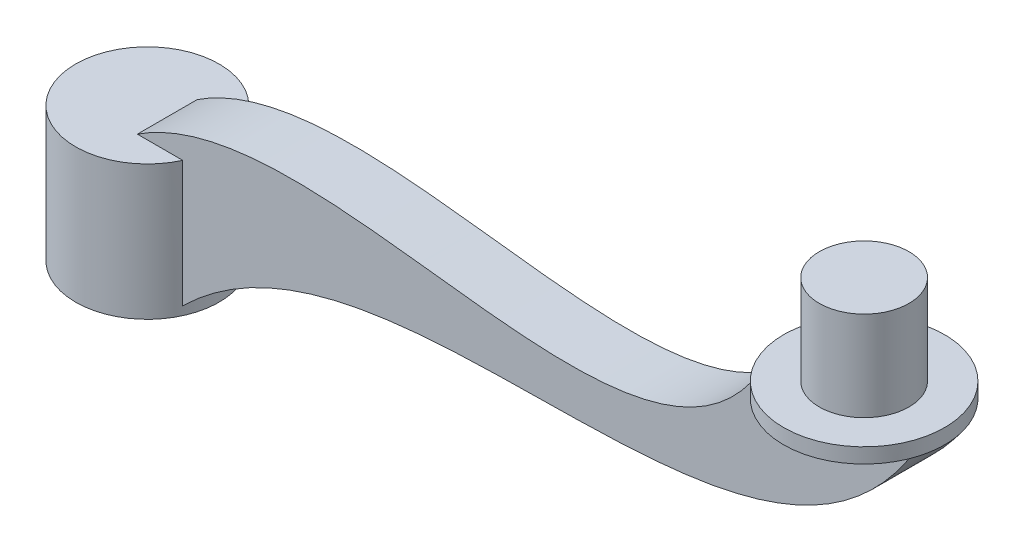
SolidWorks part; units mm, degrees
ref_plane "Front Plane" through (0, 0, 0) normal (0, 0, 1) x (1, 0, 0)
ref_plane "Top Plane" through (0, 0, 0) normal (0, 1, 0) x (1, 0, 0)
ref_plane "Right Plane" through (0, 0, 0) normal (1, 0, 0) x (0, 0, -1)
sketch "Sketch1" plane through (0, 0, 0) normal (0, 1, 0) x (1, 0, 0)
  circle A0 centre (0, 0) radius 7.5005
  circle A1 centre (0, 0) radius 12
  dimension "D1" = 15.001
extrude "Boss-Extrude1" add sketch "Sketch1" along normal blind 20 from offset 7.5
sketch "Sketch2" plane through (0, 0, 0) normal (0, 0, 1) x (1, 0, 0)
  line L0 (12, 27.5) -> (-12, 27.5) construction
  line L1 (0, 27.5) -> (8.9613, 27.5)
  line L2 (8.9613, 27.5) -> (8.9613, 6.9153)
  line L3 (107.347, 47.5) -> (132.347, 47.5)
  spline S0 degree 3 poles (0, 27.5) (29.0958, 52.4401) (86.5742, 13.532) (107.347, 47.5) knots 0 0 0 0 1 1 1 1
  spline S1 degree 3 poles (8.9613, 6.9153) (42.43, 43.6238) (104.8265, 5.8933) (132.347, 47.5) knots 0 0 0 0 1 1 1 1
  dimension "D1" = 25
  dimension "D2" = 20
extrude "Boss-Extrude2" add sketch "Sketch2" along normal mid plane 10
extrude "Boss-Extrude3" add sketch "Sketch1<2>" along normal blind 2.5 from surface contours A1 A0 | A0 region at (0, 0, 0) region at (-11.6606, 0, 0) starting at face at (-0.7502, 27.5, 0)
sketch "Sketch1<2>" plane through (0, 0, 0) normal (0, 1, 0) x (1, 0, 0) same geometry as "Sketch1"
sketch "Sketch3" plane through (0, 47.5, 0) normal (0, 1, 0) x (1, 0, 0)
  circle A0 centre (119.847, 0) radius 13.4629
  dimension "D1" = 26.9258
extrude "Boss-Extrude4" add sketch "Sketch3" along normal blind 2.5
sketch "Sketch5" plane through (0, 50, 0) normal (0, 1, 0) x (1, 0, 0)
  circle A0 centre (119.847, 0) radius 7.5
extrude "Boss-Extrude5" add sketch "Sketch5" along normal blind 15
